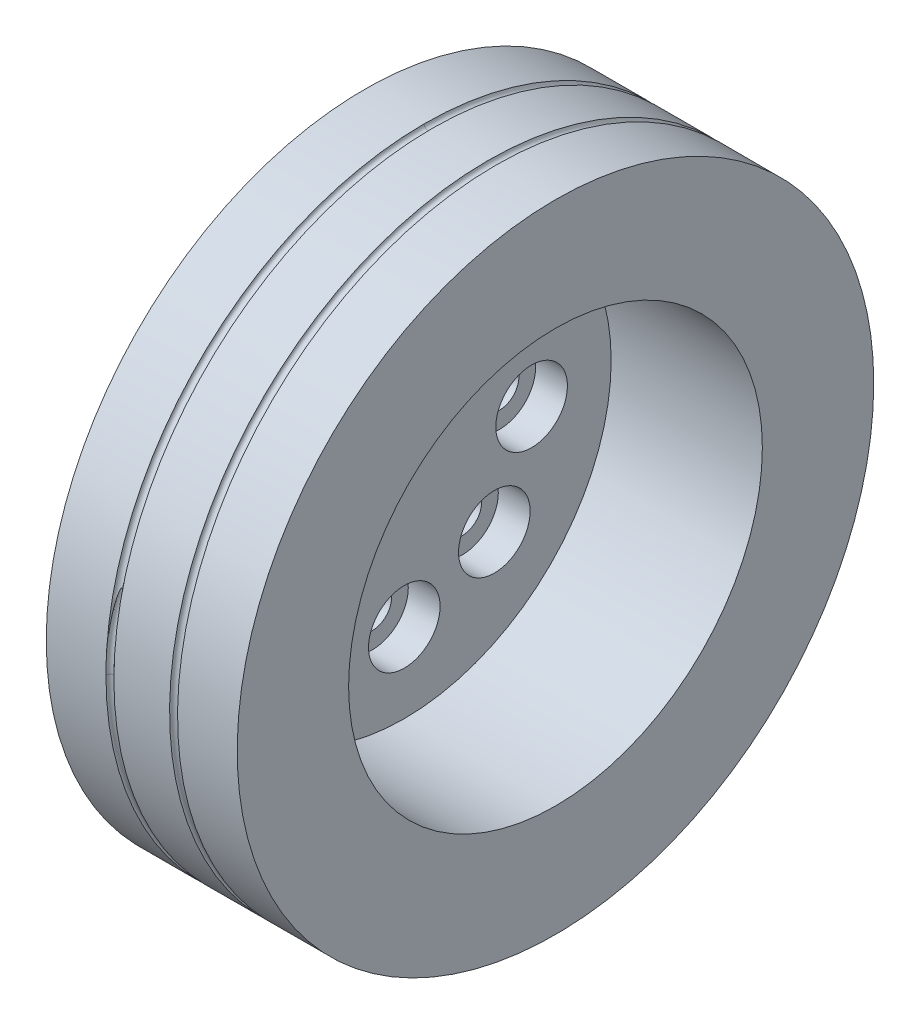
SolidWorks part; units mm, degrees
ref_plane "정면" through (0, 0, 0) normal (0, 0, 1) x (1, 0, 0)
ref_plane "윗면" through (0, 0, 0) normal (0, 1, 0) x (1, 0, 0)
ref_plane "우측면" through (0, 0, 0) normal (1, 0, 0) x (0, 0, -1)
sketch "스케치2" plane through (0, 0, 0) normal (1, 0, 0) x (0, 0, -1)
  circle A0 centre (0, 0) radius 9.75
  dimension "D1" = 19.5
extrude "보스-돌출1" add sketch "스케치2" against normal blind 5
ref_plane "평면1" through (-2.5, 0, 0) normal (1, 0, 0) x (0, 0, -1)
sketch "스케치5" plane through (-2.5, 0, 0) normal (1, 0, 0) x (0, 0, -1)
  circle A0 centre (0, 0) radius 13
extrude "보스-돌출2" add sketch "스케치5" along normal blind 2.5
sketch "스케치3" plane through (0, 0, 0) normal (1, 0, 0) x (0, 0, -1)
  circle A0 centre (0, 0) radius 8 construction
  point P3 (0, 8)
  point P6 (5.6569, 5.6569)
  point P7 (8, 0)
  point P8 (5.6569, -5.6569)
  point P9 (0, -8)
  point P10 (-5.6569, -5.6569)
  point P11 (-8, 0)
  point P12 (-5.6569, 5.6569)
  point P13 (0, 0)
  dimension "D1" = 16
  dimension "D2" = 8
hole_wizard "M2 소켓 머리 캡 나사용 카운터보어1" positions "3D스케치3" profile "스케치7" counterbore size "M2" standard "KS" end condition through all
sketch3d "3D스케치3"
  point P0 (0, 8, 0)
  point P3 (0, 5.6569, -5.6569)
  point P6 (0, 0, -8)
  point P9 (0, -5.6569, -5.6569)
  point P12 (0, -8, 0)
  point P15 (0, -5.6569, 5.6569)
  point P18 (0, 0, 8)
  point P21 (0, 5.6569, 5.6569)
sketch "스케치7" plane through (0, 8, 0) normal (0, 1, 0) x (0, 0, -1)
  line L0 (0, 0) -> (0, 5)
  line L1 (0, 5) -> (1.2, 5)
  line L3 (1.2, 5) -> (1.2, 2)
  line L4 (1.2, 2) -> (2.25, 2)
  line L5 (2.25, 2) -> (2.25, 0)
  line L7 (2.25, 0) -> (0, 0)
  line L11 (0, -6.35) -> (0, 107.95) construction
  dimension "관통 구멍 지름" = 2.4
  dimension "관통 구멍 깊이" = 5
  dimension "카운터보어 지름" = 4.5
  dimension "카운터보어 깊이" = 2
sketch "스케치8" plane through (-2.5, 0, 0) normal (1, 0, 0) x (0, 0, -1)
  circle A0 centre (0, 0) radius 13
extrude "돌출-얇게1" add sketch "스케치8" along normal blind 12 thin thin type one direction wall 7
sketch "스케치9" plane through (9.5, 0, 0) normal (1, 0, 0) x (0, 0, -1)
ref_plane "평면3" through (1.5, 0, 0) normal (-1, 0, 0) x (0, 0, 1)
sketch "스케치10" plane through (1.5, 0, 0) normal (-1, 0, 0) x (0, 0, 1)
  circle A0 centre (0, 0) radius 18
sketch "스케치11" plane through (0, 0, 0) normal (0, 0, 1) x (1, 0, 0)
  line L0 (-2.5, 20) -> (1.5, 20) construction
  line L1 (1.5, 19.8) -> (1.5, -19.8) construction
  line L2 (9.5, 20) -> (-2.5, 20) construction
  circle A0 centre (1.5, 20) radius 0.25
  dimension "D1" = 0.5
sweep "컷-스윕1" cut profiles "스케치11" path "스케치10"
ref_plane "평면5" through (3.5, 0, 0) normal (1, 0, 0) x (0, 0, -1)
mirror "대칭 복사1" about plane through (3.5, 0, 0) normal (1, 0, 0) of "컷-스윕1"
sketch "스케치12" plane through (1.5, 0, 0) normal (-1, 0, 0) x (0, 0, 1)
  circle A0 centre (0, 0) radius 20 construction
  circle A3 centre (0, 0) radius 13 construction
  circle A4 centre (0, 0) radius 13 construction
  spline S0 degree 3 poles (20, 0) (20, 6.8977) (11.1676, 12.1544) (1.5781, 13) (0, 13) knots 0 0 0 0 0.722486 1 1 1 1
  point P4 (0, 13)
  point P10 (13.0245, 9.4124)
  point P11 (20, 0)
  point P12 (0, 0)
  point P13 (0, 0)
  point P14 (0, 0)
  point P15 (6.8422, 12.191)
ref_plane "평면6" through (1.5, 0, 20) normal (0, 1, 0) x (1, 0, 0)
sketch "스케치13" plane through (1.5, 0, 20) normal (0, 1, 0) x (1, 0, 0)
  line L0 (0, 20) -> (0, 0) construction
  circle A0 centre (0, 0) radius 0.25
  dimension "D1" = 0.5
sweep "컷-스윕2" cut profiles "스케치13" path "스케치12"
